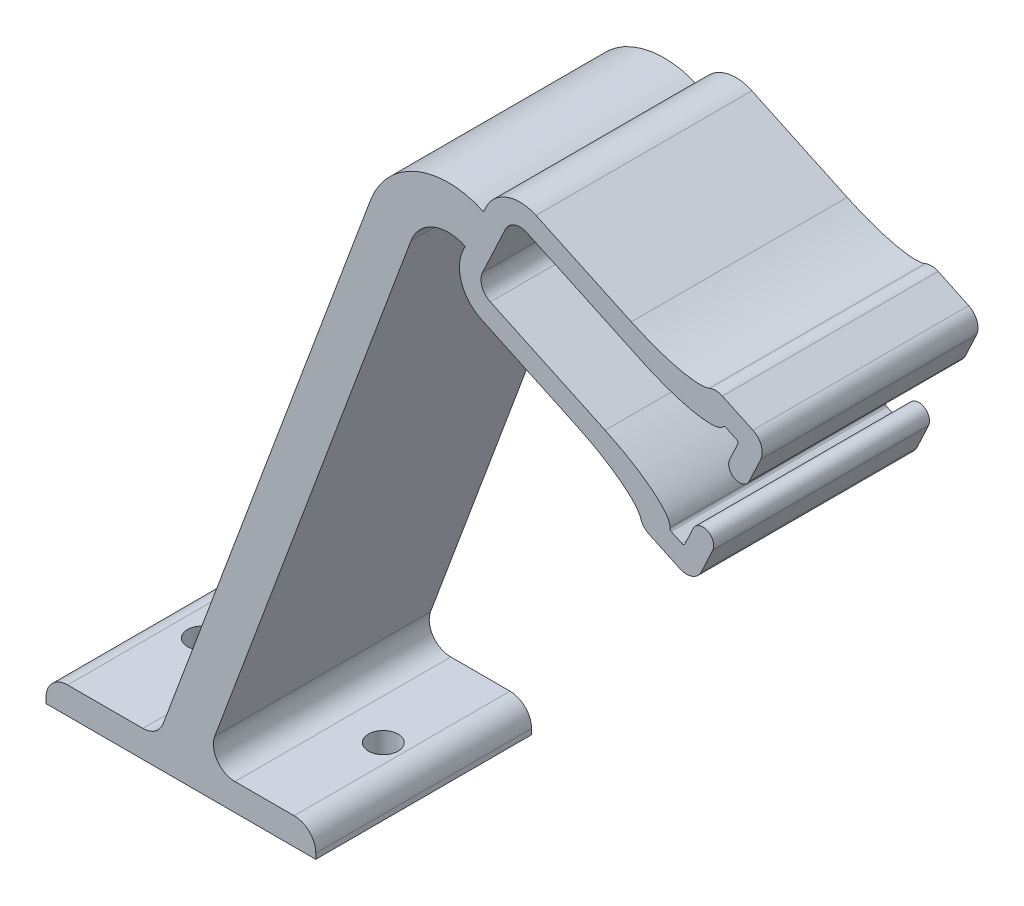
SolidWorks part; units mm, degrees
ref_plane "Front Plane" through (0, 0, 0) normal (0, 0, 1) x (1, 0, 0)
ref_plane "Top Plane" through (0, 0, 0) normal (0, 1, 0) x (1, 0, 0)
ref_plane "Right Plane" through (0, 0, 0) normal (1, 0, 0) x (0, 0, -1)
sketch "Sketch1" plane through (0, 0, 0) normal (0, 0, 1) x (1, 0, 0)
  line L0 (-14.1537, 5.9261) -> (-53.5847, -100)
  line L1 (0, 0) -> (41.217, -19.2719)
  line L2 (0, 0) -> (10.1654, 21.7409)
  line L3 (10.1654, 21.7409) -> (51.3824, 2.469)
  line L12 (41.217, -19.2719) -> (51.3824, 2.469)
  line L13 (5.3177, 1.9292) -> (42.9113, -15.6484)
  line L14 (5.3177, 1.9292) -> (12.0946, 16.4232)
  line L15 (12.0946, 16.4232) -> (49.6882, -1.1545)
  line L16 (42.9113, -15.6484) -> (49.6882, -1.1545)
  line L17 (49.6882, -1.1545) -> (45.4679, -0.7367)
  line L18 (49.6882, -1.1545) -> (53.0767, 6.0925)
  line L19 (53.0767, 6.0925) -> (49.4532, 7.7867)
  line L20 (45.4679, -0.7367) -> (49.4532, 7.7867)
  line L21 (42.9113, -15.6484) -> (39.2878, -13.9542)
  line L22 (42.9113, -15.6484) -> (39.5228, -22.8954)
  line L23 (39.5228, -22.8954) -> (35.8993, -21.2011)
  line L24 (39.2878, -13.9542) -> (35.8993, -21.2011)
  line L25 (49.4532, 7.7867) -> (59.4177, 3.1276)
  line L26 (49.4532, 7.7867) -> (47.759, 4.1632)
  line L27 (47.759, 4.1632) -> (57.7235, -0.4959)
  line L28 (59.4177, 3.1276) -> (57.7235, -0.4959)
  line L29 (35.8993, -21.2011) -> (45.8639, -25.8603)
  line L30 (35.8993, -21.2011) -> (37.5936, -17.5776)
  line L31 (37.5936, -17.5776) -> (47.5581, -22.2368)
  line L32 (45.8639, -25.8603) -> (47.5581, -22.2368)
  line L33 (57.7235, -0.4959) -> (54.1, 1.1983)
  line L34 (57.7235, -0.4959) -> (56.0293, -4.1194)
  line L35 (56.0293, -4.1194) -> (52.4058, -2.4252)
  line L36 (54.1, 1.1983) -> (52.4058, -2.4252)
  line L37 (47.5581, -22.2368) -> (43.9347, -20.5425)
  line L38 (47.5581, -22.2368) -> (49.2524, -18.6133)
  line L39 (49.2524, -18.6133) -> (45.6289, -16.9191)
  line L40 (43.9347, -20.5425) -> (45.6289, -16.9191)
  line L41 (6.7769, 14.4939) -> (3.3885, 7.247)
  line L43 (-6.6563, 3.1352) -> (-45.0484, -100)
  line L44 (-24.3165, -105) -> (-74.3165, -105)
  line L45 (-24.3165, -105) -> (-24.3165, -100)
  line L46 (-24.3165, -100) -> (-74.3165, -100)
  line L47 (-74.3165, -105) -> (-74.3165, -100)
  line L48 (-53.5847, -100) -> (-45.0484, -100)
  arc A0 (52.4058, -2.4252) -> (56.0293, -4.1194) centre (54.2175, -3.2723) ccw
  arc A1 (45.6289, -16.9191) -> (49.2524, -18.6133) centre (47.4406, -17.7662) cw
  arc A2 (-14.1537, 5.9261) -> (6.7769, 14.4939) centre (0.2618, 0.56) cw
  arc A3 (3.3885, 7.247) -> (-6.6563, 3.1352) centre (0.2618, 0.56) ccw
  point P31 (5.0827, 10.8704)
  point P35 (-49.3165, -100)
  point P44 (-49.3165, -100)
  point P45 (5.0827, 10.8704)
  dimension "D6" = 4
  dimension "D10" = 4
  dimension "D11" = 4
  dimension "D1" = 4
  dimension "D2" = 4
  dimension "D3" = 4
  dimension "D4" = 16
  dimension "D5" = 41.5
  dimension "D7" = 4
  dimension "D8" = 4
  dimension "D9" = 4
  dimension "D12" = 11
  dimension "D13" = 11
  dimension "D14" = 4
  dimension "D15" = 4
  dimension "D16" = 8
  dimension "D17" = 8
  dimension "D18" = 5
  dimension "D19" = 50
  dimension "D20" = 100
extrude "Boss-Extrude1" add sketch "Sketch1" along normal blind 40
fillet "Fillet1" radius 15 1 edges at (49.6882, -1.1545, 20)
fillet "Fillet2" radius 4 1 edges at (47.759, 4.1632, 20)
fillet "Fillet3" radius 4 1 edges at (42.9113, -15.6484, 20)
fillet "Fillet4" radius 15 1 edges at (37.5936, -17.5776, 20)
fillet "Fillet5" radius 3 4 edges at (45.8639, -25.8603, 20) (59.4177, 3.1276, 20)
fillet "Fillet6" radius 0.45 4 edges at (43.9347, -20.5425, 20) (54.1, 1.1983, 20)
fillet "Fillet8" radius 7 6 edges at (0, 0, 20) (10.1654, 21.7409, 20)
fillet "Fillet9" radius 3 2 edges at (5.3177, 1.9292, 20) (12.0946, 16.4232, 20)
fillet "Fillet10" radius 4 2 edges at (-45.0484, -100, 20) (-53.5847, -100, 20)
sketch "Sketch2" plane through (0, -100, 0) normal (0, 1, 0) x (1, 0, 0)
  line L0 (-56.3638, -20) -> (-74.3165, -20) construction
  line L3 (-56.3638, -40) -> (-56.3638, 0) construction
  line L4 (-74.3165, -40) -> (-74.3165, 0) construction
  line L5 (-24.3165, -20) -> (-39.2912, -20)
  line L6 (-24.3165, -40) -> (-24.3165, 0) construction
  line L7 (-39.2912, 0) -> (-39.2912, -40) construction
  circle A0 centre (-31.8039, -20) radius 2.75
  circle A1 centre (-65.3402, -20) radius 2.75
  dimension "D1" = 5.5
  dimension "D2" = 5.5
extrude "Cut-Extrude1" cut sketch "Sketch2" against normal through all contours L0 A1 | A1 L0 | L5 A0 | L5 A0
fillet "Fillet11" radius 4 2 edges at (-24.3165, -100, 20) (-74.3165, -100, 20)
